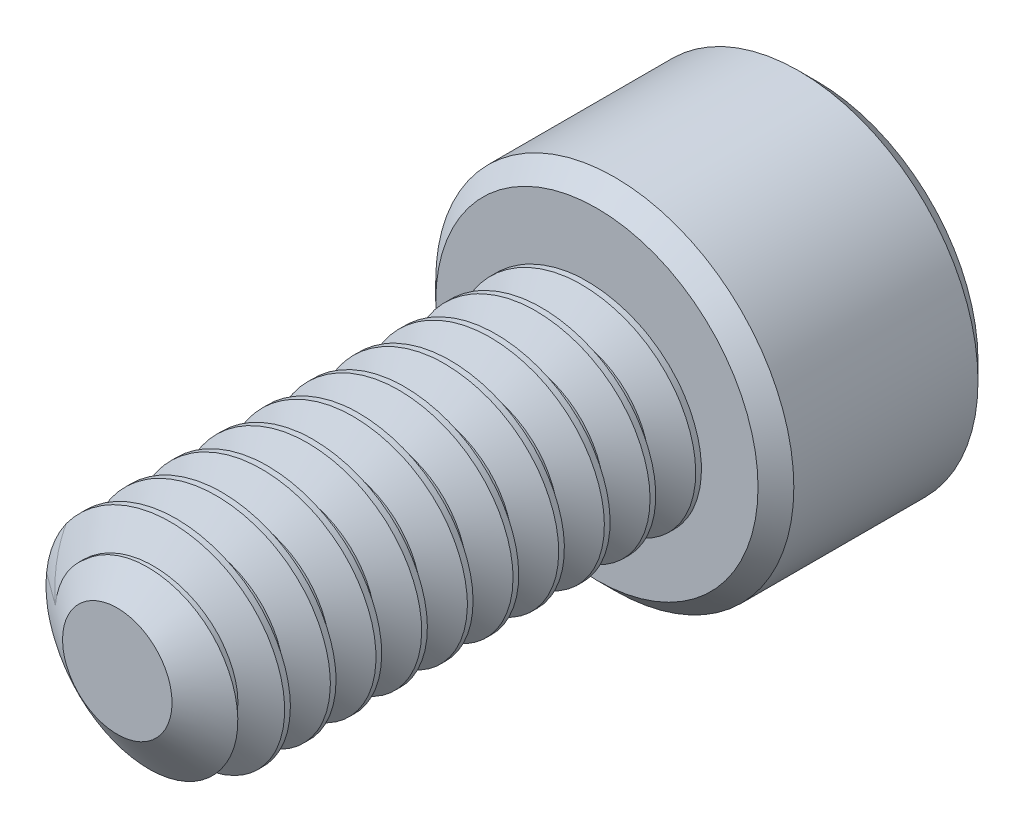
SolidWorks part; units mm, degrees
other "DetailItem1"
ref_plane "Front Plane" through (0, 0, 0) normal (0, 0, 1) x (1, 0, 0)
ref_plane "Top Plane" through (0, 0, 0) normal (0, 1, 0) x (1, 0, 0)
ref_plane "Right Plane" through (0, 0, 0) normal (1, 0, 0) x (0, 0, -1)
sketch "Sketch1" plane through (0, 0, 0) normal (0, 0, 1) x (1, 0, 0)
  circle A0 centre (0, 0) radius 1.0922
  dimension "OD" = 2.1844
extrude "Extrude1" add sketch "Sketch1" against normal blind 4.7625
sketch "Sketch2" plane through (0, 0, 0) normal (0, 0, 1) x (1, 0, 0)
  circle A0 centre (0, 0) radius 1.0922 construction
  circle A1 centre (0, 0) radius 1.0922
curve "Helix/Spiral1" pitch 0.4536 height 5.2161 radius 1.0922 centre (0, 0, 0) axis (0, 0, -1) start towards (0, 1, 0) parameters "pitch"=0.4536
sketch "Sketch3" plane through (0, 0, 0) normal (1, 0, 0) x (0, 0, -1)
  line L0 (-0.3969, 1.0922) -> (-0.2268, 0.7976)
  line L1 (-0.2268, 0.7976) -> (-0.1701, 0.7976)
  line L2 (-0.1701, 0.7976) -> (0, 1.0922)
  line L3 (-0.3969, 1.0922) -> (0, 1.0922)
  line L4 (-0.1984, 1.0922) -> (-0.1984, 0.7976) construction
  line L5 (-0.3118, 0.9449) -> (-0.085, 0.9449) construction
  line L6 (0, 1.0922) -> (0, -1.0922) construction
  dimension "D1" = 0.0567
  dimension "D2" = 0.2268
  dimension "D3" = 60
sweep "Cut-Sweep1" cut profiles "Sketch3" path "Helix/Spiral1"
sketch "Sketch4" plane through (0, 0, 0) normal (1, 0, 0) x (0, 0, -1)
  line L0 (0.3841, 1.0922) -> (0, 0.5436)
  line L1 (0, 0.5436) -> (0, 1.0922)
  line L2 (0.3841, 1.0922) -> (0, 1.0922)
  line L3 (-0.3969, 1.0922) -> (0, 1.0922) construction
  line L4 (0, 0) -> (7.0209, 0) construction
  dimension "D1" = 55
  dimension "D2" = 0.254
revolve "Cut-Revolve1" cut sketch "Sketch4" angle 360 about L4
sketch "Sketch5" plane through (0, 0, 0) normal (1, 0, 0) x (0, 0, -1)
  line L0 (4.7625, -0.7793) -> (4.7625, 0.8061) construction
  line L1 (4.7625, 1.2192) -> (0.1202, 1.2192)
  line L2 (4.7625, 1.2192) -> (4.7625, 0)
  line L3 (4.7625, 0) -> (0, 0)
  line L4 (0, 0.889) -> (0, 0)
  line L5 (0.1202, 1.2192) -> (0, 0.889)
  line L6 (0, 0) -> (9.9695, 0) construction
  point P3 (0, 1.2192)
  point P10 (0, 1.2192)
  dimension "D1" = 0.3302
  dimension "D2" = 0.127
  dimension "D3" = 20
  dimension "Min Thread" = 0
revolve "partially thread" [suppressed] add sketch "Sketch5" angle 360 about L6
sketch "Sketch6" plane through (0, 0, -4.7625) normal (0, 0, -1) x (-1, 0, 0)
  circle A0 centre (0, 0) radius 1.778
  dimension "head dia" = 3.556
extrude "Extrude2" add sketch "Sketch6" along normal blind 2.1844
sketch "Sketch7" plane through (0, 0, -6.9469) normal (0, 0, -1) x (-1, 0, 0)
  line L1 (0, 1.1457) -> (-0.9922, 0.5728)
  line L2 (-0.9922, 0.5728) -> (-0.9922, -0.5728)
  line L3 (-0.9922, -0.5728) -> (0, -1.1457)
  line L4 (0, -1.1457) -> (0.9922, -0.5728)
  line L5 (0.9922, -0.5728) -> (0.9922, 0.5728)
  line L6 (0.9922, 0.5728) -> (0, 1.1457)
  circle A0 centre (0, 0) radius 0.9922 construction
  dimension "hex dia" = 1.9844
extrude "Cut-Extrude1" cut sketch "Sketch7" against normal blind 1.4883
sketch "Sketch8" plane through (0, 0, -6.9469) normal (0, 0, -1) x (-1, 0, 0)
  circle A0 centre (0, 0) radius 1.1457
extrude "Cut-Extrude2" cut sketch "Sketch8" against normal through all draft 45
chamfer "Chamfer1" distance 0.1778 angle 45 2 edges at (-1.778, 0, -6.9469) (-1.778, 0, -4.7625)
sketch "Sketch9" plane through (0, 0, 0) normal (1, 0, 0) x (0, 0, -1)
  line L0 (0, 1.0922) -> (0, -1.0922) construction
  line L1 (1.1339, 1.0922) -> (1.1339, -1.0922) construction
  dimension "D1" = 1.1339
  dimension "D4" = 0.635
  dimension "D5" = 0.3302
equation "\"D3@Helix/Spiral1\" = \"screw length@Extrude1\"+\"pitch@Helix/Spiral1\""
equation "\"D1@Sketch3\" = \"pitch@Helix/Spiral1\"*.125"
equation "\"D2@Sketch3\" = \"pitch@Helix/Spiral1\"*.5"
equation "\"D1@Cut-Extrude1\" = \"hex dia@Sketch7\"*.75"
equation "\"D1@Chamfer1\" = \"head dia@Sketch6\"*.05"
equation "\"D1@Sketch9\" = \"pitch@Helix/Spiral1\"*2.5"
